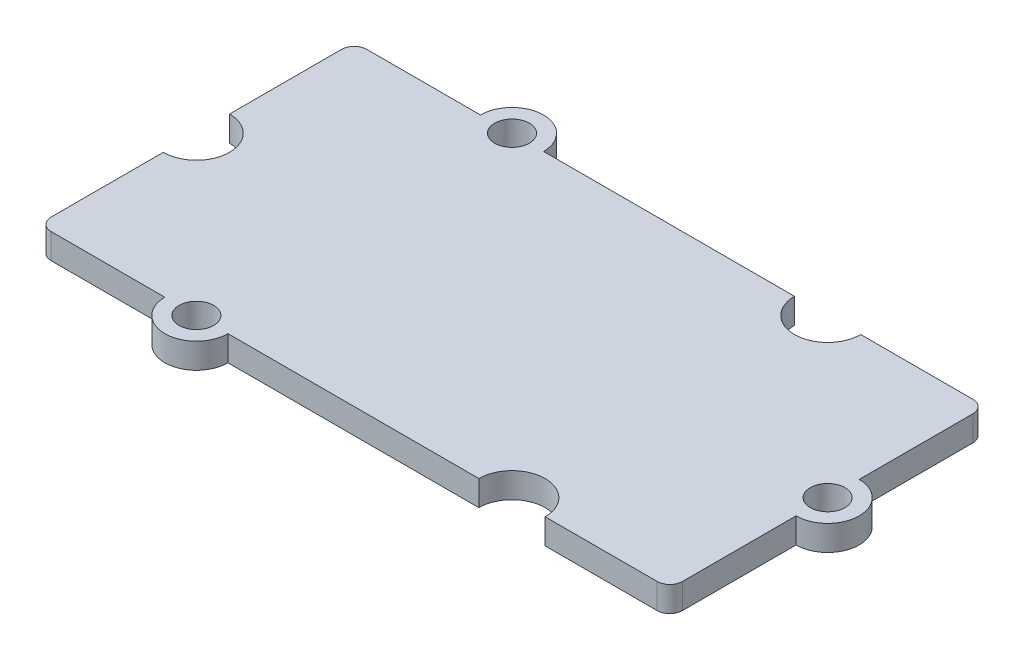
SolidWorks part; units mm, degrees
ref_plane "Plan de face" through (0, 0, 0) normal (0, 0, 1) x (1, 0, 0)
ref_plane "Plan de dessus" through (0, 0, 0) normal (0, 1, 0) x (1, 0, 0)
ref_plane "Plan de droite" through (0, 0, 0) normal (1, 0, 0) x (0, 0, -1)
sketch "Esquisse1" plane through (0, 0, 0) normal (0, 1, 0) x (1, 0, 0)
  line L1 (-19.2, -10) -> (19.2, -10)
  line L2 (-20, -9.2) -> (-20, 9.2)
  line L3 (-19.2, 10) -> (19.2, 10)
  line L4 (20, -9.2) -> (20, 9.2)
  line L5 (-20, -10) -> (20, 10) construction
  line L6 (-20, 10) -> (20, -10) construction
  circle A0 centre (-10, 10) radius 2
  circle A1 centre (-10, -10) radius 2
  circle A2 centre (-20, 0) radius 2.1
  circle A3 centre (10, 10) radius 2.1
  circle A4 centre (-10, 10) radius 1.1
  arc A5 (19.2, 10) -> (20, 9.2) centre (19.2, 9.2) cw
  circle A6 centre (-10, -10) radius 1.1
  arc A7 (-19.2, -10) -> (-20, -9.2) centre (-19.2, -9.2) cw
  arc A8 (19.2, -10) -> (20, -9.2) centre (19.2, -9.2) ccw
  arc A9 (-20, 9.2) -> (-19.2, 10) centre (-19.2, 9.2) cw
  circle A10 centre (10, -10) radius 2.1
  circle A11 centre (20, 0) radius 2
  circle A12 centre (20, 0) radius 1.1
  point P0 (0, 0)
  dimension "D2" = 0.8
  dimension "D3" = 4.2
  dimension "D4" = 2.2
  dimension "D5" = 4
  dimension "D7" = 10
  dimension "D8" = 30
  dimension "D1" = 40
  dimension "D6" = 20
extrude "Boss.-Extru.1" add sketch "Esquisse1" along normal mid plane 1.6 contours A9 L2 A2 A7 L1 A1 A8 L4 A3 A5 L3 A0 | A4 L3 A0 | A4 L3 A0 | A6 L1 A1 | A6 L1 A1 | A12 L4 A11 | A12 L4 A11 region at (-10, 0, 8.8553) region at (-8.45, 0, 10.0447) region at (-0.0011, 0, 0) region at (18.0447, 0, 0) region at (20.0447, 0, 1.55) region at (-10, 0, -11.9553) region at (-11.55, 0, -9.9553)
